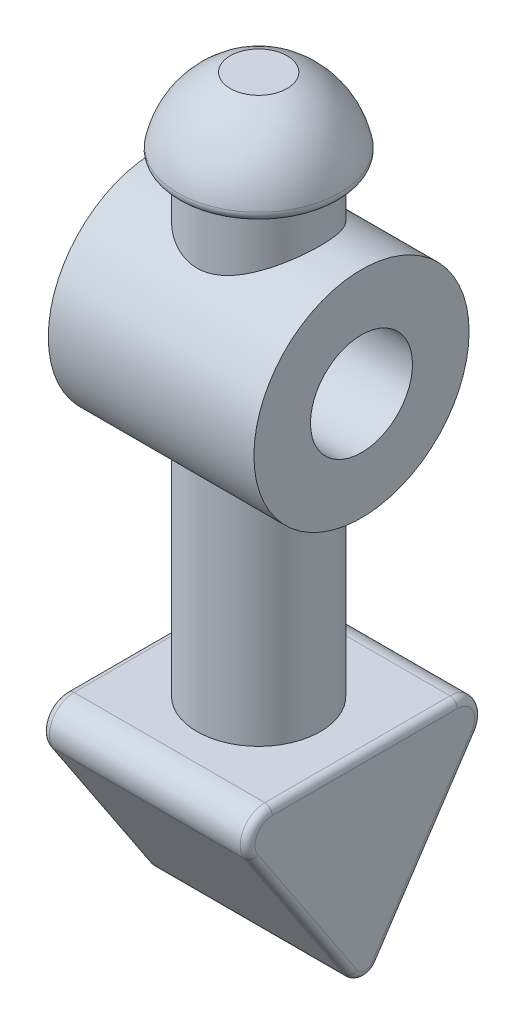
SolidWorks part; units mm, degrees
ref_plane "Front Plane" through (0, 0, 0) normal (0, 0, 1) x (1, 0, 0)
ref_plane "Top Plane" through (0, 0, 0) normal (0, 1, 0) x (1, 0, 0)
ref_plane "Right Plane" through (0, 0, 0) normal (1, 0, 0) x (0, 0, -1)
sketch "Sketch1" plane through (0, 0, 0) normal (1, 0, 0) x (0, 0, -1)
  circle A0 centre (0, 0) radius 16.6116
  dimension "D1" = 33.2232
extrude "Boss-Extrude1" add sketch "Sketch1" along normal blind 31.75
ref_plane "Plane1" through (2.54, 0, 0) normal (1, 0, 0) x (0, 0, -1)
ref_plane "Plane2" through (29.21, 0, 0) normal (1, 0, 0) x (0, 0, -1)
sketch "Sketch5" plane through (0, 0, 0) normal (-1, 0, 0) x (0, 0, 1)
  circle A0 centre (0, 0) radius 7.874
  dimension "D1" = 15.748
extrude "Cut-Extrude4" cut sketch "Sketch5" against normal up to surface (31.75 mm away) up to face at (31.75, 0, -16.6116)
ref_plane "Plane4" through (0, 16.6116, 0) normal (0, 1, 0) x (1, 0, 0)
ref_plane "Plane5" through (0, 23.6322, 0) normal (0, 1, 0) x (1, 0, 0)
sketch "Sketch7" plane through (0, 23.6322, 0) normal (0, 1, 0) x (1, 0, 0)
  line L0 (15.875, 15.7988) -> (15.875, -15.7988) construction
  circle A0 centre (15.875, 0) radius 9.525
  dimension "D1" = 19.05
extrude "Boss-Extrude2" add sketch "Sketch7" against normal blind 14.732
sketch "Sketch8" plane through (0, 23.6322, 0) normal (0, 1, 0) x (1, 0, 0)
  circle A0 centre (15.875, 0) radius 12.7
  dimension "D1" = 25.4
extrude "Boss-Extrude3" add sketch "Sketch8" along normal blind 11.43
sketch "Sketch9" plane through (0, 35.0622, 0) normal (0, 1, 0) x (1, 0, 0)
  circle A0 centre (15.875, 0) radius 6.858
sketch "Sketch10" plane through (0, 0, 0) normal (0, 0, 1) x (1, 0, 0)
  line L0 (11.4874, 35.0622) -> (3.175, 35.0622)
  line L1 (3.175, 35.0622) -> (3.175, 23.6322)
  line L2 (15.875, 35.0622) -> (15.875, 19.0536) construction
  line L3 (3.175, 35.0622) -> (3.175, 23.6322) construction
  line L4 (3.175, 23.6322) -> (28.575, 23.6322) construction
  arc A0 (11.4874, 35.0622) -> (3.175, 23.6322) centre (16.76, 22.4901) ccw
  dimension "D1" = 0
revolve "Cut-Revolve1" cut sketch "Sketch10" angle 360 about L2
fillet "Fillet5" radius 1.27 1 edges at (15.875, 23.6322, 12.7)
sketch "Sketch11" plane through (0, 0, 0) normal (0, 0, 1) x (1, 0, 0)
  line L0 (15.875, 35.0622) -> (15.875, -72.8878) construction
ref_plane "Plane6" through (15.875, 0, 0) normal (1, 0, 0) x (0, 0, -1)
sketch "Sketch12" plane through (15.875, 0, 0) normal (1, 0, 0) x (0, 0, -1)
  line L0 (0.5127, -78.534) -> (0.5127, -31.0337) construction
  line L1 (2.6291, -77.3984) -> (7.3131, -70.3406)
  line L2 (-13.7709, -48.3616) -> (14.7981, -48.3616)
  line L3 (-22.9, -16.6116) -> (22.7687, -16.6116) construction
  line L5 (-16.9456, -54.2782) -> (-6.2871, -70.3406)
  line L8 (17.9726, -54.2784) -> (7.3131, -70.3406)
  line L9 (-6.2871, -70.3406) -> (-1.6037, -77.3984)
  arc A0 (17.9726, -54.2784) -> (14.7981, -48.3616) centre (14.7981, -52.1716) ccw
  arc A1 (2.6291, -77.3984) -> (-1.6037, -77.3984) centre (0.5127, -75.994) cw
  arc A2 (-16.9456, -54.2782) -> (-13.7709, -48.3616) centre (-13.7709, -52.1716) cw
  circle A3 centre (0, 0) radius 16.6116 construction
  dimension "D1" = 2.54
  dimension "D2" = 3.81
  dimension "D5" = 7.62
  dimension "D3" = 33.567
  dimension "D4" = 33.57
  dimension "D6" = 28.569
  dimension "D7" = 31.75
extrude "Boss-Extrude4" add sketch "Sketch12" along normal blind 15.875 and the other way blind 15.875 separate body
ref_plane "Plane7" through (0, -16.6116, 0) normal (0, -1, 0) x (-1, 0, 0)
sketch "Sketch13" plane through (0, -16.6116, 0) normal (0, -1, 0) x (-1, 0, 0)
  circle A0 centre (-15.875, 0) radius 9.525
  dimension "D1" = 19.05
extrude "Boss-Extrude5" add sketch "Sketch13" along normal blind 31.75 and the other way blind 3.81
ref_plane "Plane8" through (0, 0, -11.43) normal (0, 0, 1) x (1, 0, 0)
ref_plane "Plane9" through (0, 0, 11.43) normal (0, 0, 1) x (1, 0, 0)
fillet "Fillet6" radius 1.143 12 edges at (0, -65.8384, -10.3009) (31.75, -65.8384, -10.3009) (0, -78.534, -0.5127) (0, -65.8383, 9.2746) (0, -50.3702, 17.1282) (0, -48.3616, -0.5136) (0, -50.3703, -18.1554) (31.75, -78.534, -0.5127) (31.75, -65.8383, 9.2746) (31.75, -50.3702, 17.1282) (31.75, -48.3616, -0.5136) (31.75, -50.3703, -18.1554)
ref_plane "Plane14" through (6.35, 0, 0) normal (1, 0, 0) x (0, 0, -1)
sketch "Sketch14" [suppressed] plane through (31.75, 0, 0) normal (1, 0, 0) x (0, 0, -1)
  line L0 (-28.1309, -78.534) -> (45.8355, -78.534) construction
  circle A0 centre (0, 0) radius 16.6116 construction
  arc A1 (-1.6037, -77.3984) -> (2.6291, -77.3984) centre (0.5127, -75.994) ccw construction
  dimension "D1" = 78.534
